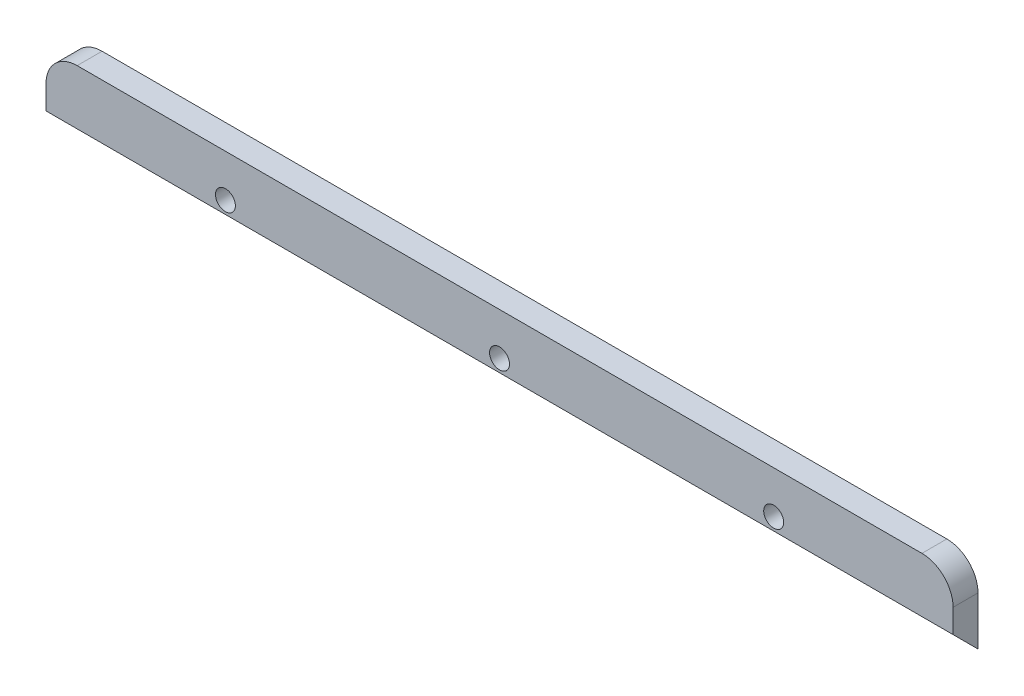
SolidWorks part; units mm, degrees
material "6061-T6 (SS)"
ref_plane "Front Plane" through (0, 0, 0) normal (0, 0, 1) x (1, 0, 0)
ref_plane "Top Plane" through (0, 0, 0) normal (0, 1, 0) x (1, 0, 0)
ref_plane "Right Plane" through (0, 0, 0) normal (1, 0, 0) x (0, 0, -1)
sketch "Sketch1" plane through (0, 0, 0) normal (1, 0, 0) x (0, 0, -1)
  line L0 (-3.0983, 0) -> (1.226, 0) construction
  line L1 (0, -3.2) -> (-2, -1.2)
  line L2 (0, -3.2) -> (0, 3.2)
  line L4 (-2, -1.2) -> (-2, 3.2)
  line L5 (-2, 3.2) -> (0, 3.2)
  dimension "D1" = 2
  dimension "D2" = 45
  dimension "D3" = 6.4
extrude "Boss-Extrude1" add sketch "Sketch1" along normal mid plane 72.8
sketch "Sketch4" [suppressed] plane through (0, 0, 0) normal (0, 0, 1) x (1, 0, 0)
  line L1 (7.5, 1.5) -> (-7.5, 1.5)
  line L2 (7.5, 1.5) -> (7.5, -3.2)
  line L3 (7.5, -3.2) -> (-7.5, -3.2)
  line L4 (-7.5, 1.5) -> (-7.5, -3.2)
  line L5 (0, 7.7759) -> (0, -8.8374) construction
  line L8 (-7.5, -3.2) -> (-7.5, 0.8) construction
  dimension "D1" = 4.7
hole_wizard "M2x0.4 Tapped Hole1" positions "Sketch2" profile "Sketch3" tap size "M2x0.4" standard "ANSI Metric" end condition through all
sketch "Sketch2" plane through (0, 0, 2) normal (0, 0, 1) x (1, 0, 0)
  circle A4 centre (-22, -0.2) radius 1.2 construction
  circle A5 centre (-22, -0.2) radius 1.2
  circle A6 centre (0, -0.2) radius 1.2 construction
  circle A7 centre (0, -0.2) radius 1.2
  circle A8 centre (22, -0.2) radius 1.2 construction
  circle A9 centre (22, -0.2) radius 1.2
  point P22 (-22, -0.2)
  point P25 (0, -0.2)
  point P28 (22, -0.2)
  point P39 (0, 0)
  point P40 (0, 0)
  point P41 (0, 0)
sketch "Sketch3" plane through (-22, -0.2, 2) normal (1, 0, 0) x (0, -1, 0)
  line L0 (0, 0) -> (0, 2)
  line L1 (0, 2) -> (0.8, 2)
  line L2 (0.8, 2) -> (0.8, 0)
  line L5 (0.8, 0) -> (0, 0)
  line L11 (0, -6.35) -> (0, 107.95) construction
  dimension "Thru Tap Drill Dia." = 1.6
  dimension "Thru Tap Drill Depth" = 2
cosmetic thread "Hole Thread4" parameters "D2"=2
cosmetic thread "Hole Thread5" parameters "D2"=2
cosmetic thread "Hole Thread6" parameters "D2"=2
extrude "Cut-Extrude4" [suppressed] cut sketch "Sketch4" along normal through all
fillet "Fillet3" radius 2.5 2 edges at (-36.4, 3.2, 1) (36.4, 3.2, 1)
